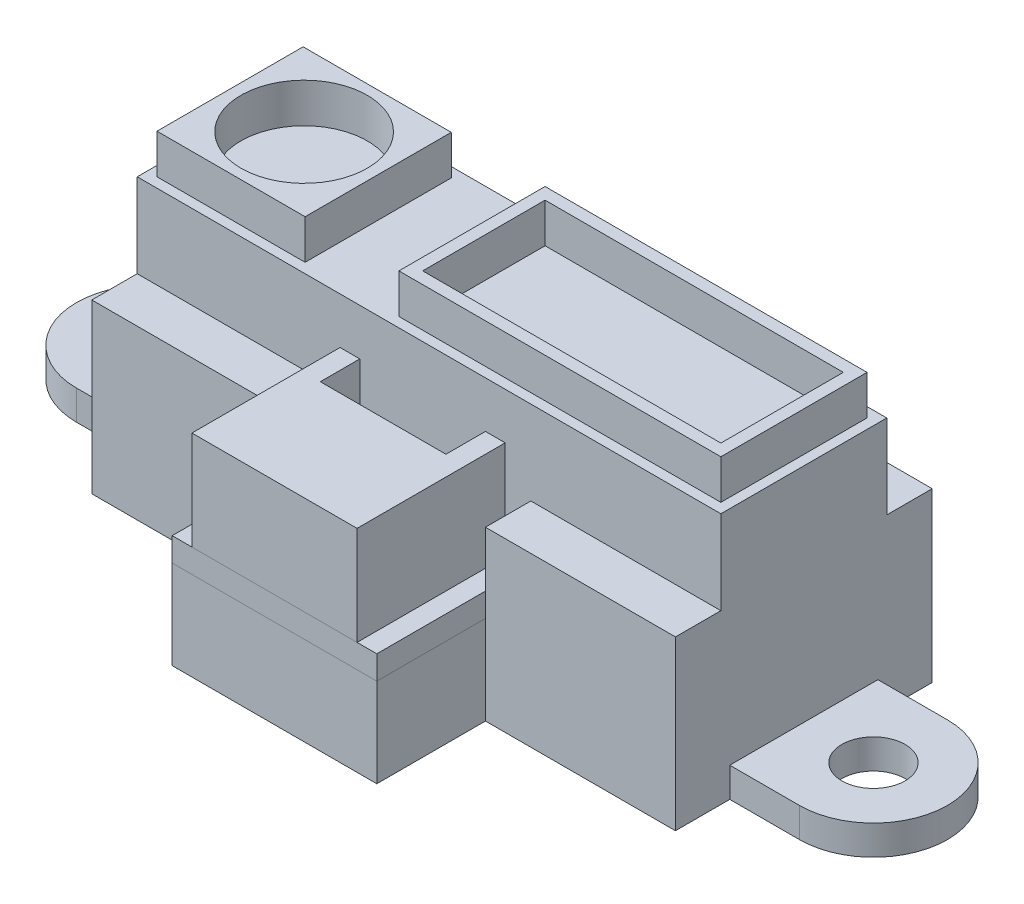
SolidWorks part; units mm, degrees
ref_plane "Front" through (0, 0, 0) normal (0, 0, 1) x (1, 0, 0)
ref_plane "Top" through (0, 0, 0) normal (0, 1, 0) x (1, 0, 0)
ref_plane "Right" through (0, 0, 0) normal (1, 0, 0) x (0, 0, -1)
sketch "Sketch1" plane through (0, 0, 0) normal (0, 1, 0) x (1, 0, 0)
  line L1 (0, 0) -> (29.55, 0)
  line L2 (0, 0) -> (0, 13)
  line L3 (0, 13) -> (29.55, 13)
  line L4 (29.55, 0) -> (29.55, 13)
  dimension "D1" = 29.55
  dimension "D2" = 13
extrude "Boss-Extrude1" add sketch "Sketch1" along normal blind 8.5
sketch "Sketch2" plane through (0, 8.5, 0) normal (0, 1, 0) x (1, 0, 0)
  line L0 (0, 2.3) -> (0, 10.7)
  line L1 (0, 13) -> (0, 0) construction
  line L2 (0, 10.7) -> (29.55, 10.7)
  line L3 (29.55, 0) -> (29.55, 13) construction
  line L4 (29.55, 10.7) -> (29.55, 2.3)
  line L5 (29.55, 2.3) -> (0, 2.3)
  line L6 (29.55, 13) -> (0, 13) construction
  dimension "D1" = 8.4
  dimension "D2" = 2.3
extrude "Boss-Extrude2" add sketch "Sketch2" along normal blind 4.25
sketch "Sketch4" plane through (0, 0, 0) normal (0, -1, 0) x (1, 0, 0)
  line L0 (14.775, 0) -> (14.775, -13) construction
  line L1 (0, 0) -> (29.55, 0) construction
  line L2 (0, -6.5) -> (36.825, -6.5) construction
  line L3 (0, -13) -> (0, 0) construction
  line L4 (36.825, 4.1579) -> (36.825, -6.5) construction
  line L5 (0, -6.5) -> (-7.275, -6.5) construction
  line L6 (-3.525, -10.25) -> (0, -10.25)
  line L7 (0, -10.7) -> (0, -2.3) construction
  line L8 (-7.275, 4.1579) -> (-7.275, -6.5) construction
  line L9 (-3.525, -2.75) -> (0, -2.75)
  line L10 (33.075, -2.75) -> (29.55, -2.75)
  line L11 (29.55, -2.3) -> (29.55, -10.7) construction
  line L12 (33.075, -10.25) -> (29.55, -10.25)
  line L13 (29.55, -13) -> (0, -13) construction
  arc A0 (-3.525, -2.75) -> (-3.525, -10.25) centre (-3.525, -6.5) ccw
  arc A1 (33.075, -2.75) -> (33.075, -10.25) centre (33.075, -6.5) cw
  circle A2 centre (-3.525, -6.5) radius 1.6
  circle A3 centre (33.075, -6.5) radius 1.6
  line M1 (0, 0) -> (0, -13)
  line M9 (29.55, -13) -> (29.55, 0)
  dimension "D1" = 3.75
  dimension "D3" = 3.2
  dimension "D2" = 36.6
extrude "Boss-Extrude5" add sketch "Sketch4" against normal blind 1.5 contours M9 | A2 M1 region at (-7.1705, 0, -6.5) region at (36.7205, 0, -6.5)
sketch "Sketch5" plane through (0, 8.5, 0) normal (0, 1, 0) x (1, 0, 0)
  line L0 (9.57, 2.3) -> (19.93, 2.3)
  line L1 (0, 2.3) -> (29.55, 2.3) construction
  line L2 (19.93, 2.3) -> (19.93, 0)
  line L3 (0, 0) -> (29.55, 0) construction
  line L4 (19.93, 0) -> (9.57, 0)
  line L5 (9.57, 0) -> (9.57, 2.3)
  line L6 (0, 2.3) -> (29.55, 2.3) construction
  line L7 (0, 2.3) -> (0, 0) construction
  point P14 (14.75, 2.3)
  dimension "D1" = 10.36
  dimension "D2" = 14.75
extrude "Cut-Extrude2" cut sketch "Sketch5" against normal blind 4
sketch "Sketch6" plane through (0, 0, 0) normal (0, 0, 1) x (1, 0, 0)
  line L0 (0, 0) -> (36.825, 0) construction
  line L2 (19.93, 4.5) -> (19.93, 0)
  line L3 (19.93, 4.5) -> (9.57, 4.5)
  line L4 (9.57, 4.5) -> (9.57, 0)
  line L5 (19.93, 4.5) -> (19.93, 8.5) construction
  line L7 (9.57, 0) -> (19.93, 0)
  line L8 (9.57, 4.5) -> (9.57, 8.5) construction
  dimension "D3" = 4.5
extrude "Boss-Extrude6" add sketch "Sketch6" along normal blind 5.5
sketch "Sketch7" plane through (0, 0, -2.3) normal (0, 0, 1) x (1, 0, 0)
  line L0 (9.57, 4.5) -> (9.57, 5.7)
  line L1 (9.57, 4.5) -> (9.57, 8.5) construction
  line L2 (9.57, 5.7) -> (19.93, 5.7)
  line L3 (19.93, 4.5) -> (19.93, 8.5) construction
  line L4 (19.93, 5.7) -> (19.93, 4.5)
  line L5 (19.93, 4.5) -> (9.57, 4.5)
  dimension "D1" = 1.2
extrude "Boss-Extrude8" add sketch "Sketch7" along normal up to surface (7.8 mm away) separate body up to face at (14.75, 2.25, 5.5)
sketch "Sketch8" plane through (0, 5.7, 0) normal (0, 1, 0) x (1, 0, 0)
  line L0 (10.57, 2) -> (10.57, -5.5)
  line L1 (19.93, -5.5) -> (9.57, -5.5) construction
  line L2 (10.57, -5.5) -> (18.93, -5.5)
  line L3 (18.93, -5.5) -> (18.93, 2)
  line L4 (18.93, 2) -> (17.93, 2)
  line L5 (17.93, 2) -> (17.93, 0)
  line L6 (17.93, 0) -> (11.57, 0)
  line L7 (11.57, 0) -> (11.57, 2)
  line L8 (11.57, 2) -> (10.57, 2)
  line L9 (19.93, -5.5) -> (19.93, 0) construction
  line L10 (9.57, -5.5) -> (9.57, 2.3) construction
  dimension "D1" = 1
  dimension "D2" = 1
  dimension "D3" = 1
  dimension "D4" = 1
  dimension "D5" = 2
  dimension "D6" = 2
  dimension "D7" = 5.5
extrude "Boss-Extrude9" add sketch "Sketch8" along normal blind 5 separate body
sketch "Sketch9" plane through (0, 12.75, 0) normal (0, 1, 0) x (1, 0, 0)
  line L0 (29.55, 10.25) -> (29.55, 2.75) construction
  line L1 (0.5, 10.2) -> (8, 10.2)
  line L2 (0.5, 10.2) -> (0.5, 2.8)
  line L3 (0.5, 2.8) -> (8, 2.8)
  line L4 (29.05, 10.2) -> (29.05, 2.8)
  line L5 (0, 2.75) -> (0, 10.25) construction
  line L6 (29.55, 10.7) -> (0, 10.7) construction
  line L7 (0, 2.3) -> (29.55, 2.3) construction
  line L8 (12.75, 10.2) -> (12.75, 2.8)
  line L9 (8, 10.2) -> (8, 2.8)
  line L10 (12.75, 2.8) -> (29.05, 2.8)
  line L11 (12.75, 10.2) -> (29.05, 10.2)
  line L12 (4.25, 10.2) -> (4.25, 2.8) construction
  line L13 (13.35, 9.6) -> (28.45, 9.6)
  line L14 (13.35, 9.6) -> (13.35, 3.4)
  line L15 (13.35, 3.4) -> (28.45, 3.4)
  line L16 (28.45, 9.6) -> (28.45, 3.4)
  line L17 (8, 6.5) -> (0.5, 6.5) construction
  circle A0 centre (4.25, 6.5) radius 3.2
  dimension "D11" = 6.4
  dimension "D1" = 0.5
  dimension "D2" = 0.5
  dimension "D3" = 0.5
  dimension "D4" = 0.5
  dimension "D5" = 16.3
  dimension "D6" = 7.5
  dimension "D7" = 0.6
  dimension "D8" = 0.6
  dimension "D9" = 0.6
  dimension "D10" = 0.6
extrude "Boss-Extrude10" add sketch "Sketch9" along normal blind 2
